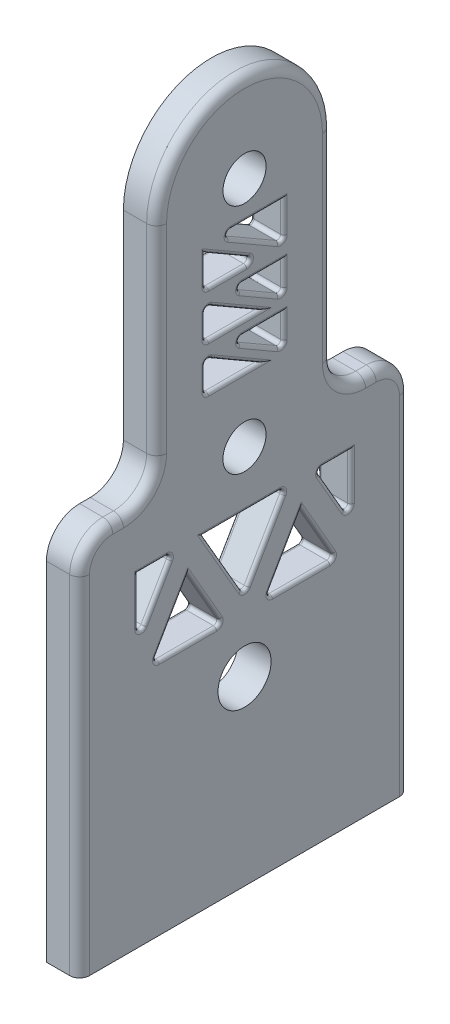
SolidWorks part; units mm, degrees
note: The reader was unsure of these and kept them because the rebuilt part matched: shared geometry of "Sketch2<15>".
ref_plane "Front Plane" through (0, 0, 0) normal (0, 0, 1) x (1, 0, 0)
ref_plane "Top Plane" through (0, 0, 0) normal (0, 1, 0) x (1, 0, 0)
ref_plane "Right Plane" through (0, 0, 0) normal (1, 0, 0) x (0, 0, -1)
sketch "Sketch2" plane through (0, 0, 0) normal (1, 0, 0) x (0, 0, -1)
  line L0 (-49.7, 0) -> (-49.7, -54.7)
  line L1 (-49.7, -54.7) -> (49.7, -54.7)
  line L2 (49.7, -54.7) -> (49.7, 0)
  line L3 (-49.7, -37.7) -> (49.7, -37.7)
  line L4 (-49.7, 0) -> (-49.7, 130)
  line L6 (49.7, 130) -> (49.7, 0)
  line L7 (-4.0065, 60) -> (3.9935, 60) construction
  line L8 (-0.0065, 60) -> (0, 130) construction
  line L9 (0, -54.7) -> (0, -37.7) construction
  line L10 (-49.7, 130) -> (49.7, 130) construction
  arc A137 (49.7, 130) -> (-49.7, 130) centre (0, 130) ccw
  circle A138 centre (-0.0065, 60) radius 6.5
  circle A139 centre (0, 130) radius 6.5
  circle A140 centre (0, 0) radius 8
  dimension "D1" = 130
  dimension "D4" = 17
  dimension "D2" = 54.7
  dimension "D3" = 70
extrude "Boss-Extrude1" add sketch "Sketch2" along normal blind 10 contours L6 A137 L4 L0 L3 L2 A140 A139 A138
sketch "Sketch10" plane through (0, 0, 0) normal (-1, 0, 0) x (0, 0, 1)
  line L0 (0, 130) -> (0.0065, 60) construction
  line L1 (0.0065, 60) -> (49.7, 60) construction
  line L2 (26.5, 130) -> (26.5, 60)
  line L3 (-49.7, 130) -> (-49.7, -54.7)
  line L4 (-49.7, -54.7) -> (49.7, -54.7)
  line L5 (49.7, -54.7) -> (49.7, 130)
  line L8 (49.7, 60) -> (49.7, 130)
  line L9 (26.5, 60) -> (49.7, 60)
  line L10 (-26.4871, 59.9951) -> (-49.6871, 59.9908)
  line L11 (-26.5, 129.9951) -> (-26.4871, 59.9951)
  line L14 (-49.7, 130) -> (-51.6635, 100)
  line L15 (-51.6635, 100) -> (-51.6635, 59.984)
  line L16 (-51.6635, 59.984) -> (-49.6871, 59.9908)
  line L20 (-49.7, -54.7) -> (49.7, -54.7)
  arc A1 (49.7, 130) -> (-49.7, 130) centre (0, 130) ccw
  arc A2 (49.7, 130) -> (-49.7, 130) centre (0, 130) ccw
  circle A4 centre (0.0065, 60) radius 6.5
  circle A5 centre (0, 130) radius 6.5
  arc A6 (26.5, 130) -> (-26.5, 129.9951) centre (0, 130) ccw
  dimension "D2" = 20
  dimension "D1" = 0
extrude "Cut-Extrude1" cut sketch "Sketch10" against normal blind 10
fillet "Fillet1" radius 10 2 edges at (5, 60, 26.5) (5, 59.9951, -26.4871)
fillet "Fillet2" radius 10 2 edges at (5, 60, 49.7) (5, 59.9908, -49.7)
fillet "Fillet4" radius 3 11 edges at (10, 100, 26.5) (10, 62.9289, 29.4289) (10, 60, 38.1) (10, 57.0711, 46.7711) (10, -2.35, 49.7) (10, -2.3537, -49.7) (10, 57.0631, -46.7717) (10, 59.993, -38.0945) (10, 62.9235, -29.4166) (10, 99.9951, -26.4945) (10, 156.5, -0.0024)
sketch "Sketch11" plane through (10, 0, 0) normal (1, 0, 0) x (0, 0, -1)
  line L0 (-0.0065, 60) -> (0, 43) construction
  line L2 (-32.0845, 43) -> (32.0845, 43)
  line L3 (-32.0845, 43) -> (-32.0845, 17)
  line L4 (-32.0845, 17) -> (32.0845, 17)
  line L5 (32.0845, 43) -> (32.0845, 17)
  line L8 (0, 43) -> (0, 17) construction
  line L11 (-27.4657, 17) -> (-17.0734, 35)
  line L12 (-17.0734, 35) -> (-6.6811, 17)
  line L13 (32.0845, 25) -> (21.6922, 43)
  line L14 (12.4546, 43) -> (-1.4018, 19)
  line L15 (-32.0845, 25) -> (-21.6922, 43)
  line L16 (-12.4546, 43) -> (1.4018, 19)
  line L17 (27.4657, 17) -> (17.0734, 35)
  line L18 (17.0734, 35) -> (5.5264, 15)
  point P4 (0, 30)
extrude "Cut-Extrude2" cut sketch "Sketch11" against normal blind 10 contours L17 L18 L4 | L13 L5 L2 | L2 L16 L14 | L12 L11 L4 | L3 L15 L2
fillet "Fillet5" radius 1 40 edges at (0, 34, 32.0845) (10, 34, 32.0845) (0, 43, 26.8883) (10, 43, 26.8883) (0, 26, 22.2695) (10, 26, 22.2695) (0, 26, 11.8772) (10, 26, 11.8772) (0, 32.214, 6.2273) (10, 32.214, 6.2273) (0, 43, 0) (10, 43, 0) (0, 26, -11.8772) (10, 26, -11.8772) (0, 26, -22.2695) (10, 26, -22.2695) (0, 43, -26.8883) (10, 43, -26.8883) (0, 34, -32.0845) (10, 34, -32.0845) (5, 25, 32.0845) (0, 34, 26.8883) (5, 43, 21.6922) (10, 34, 26.8883) (5, 17, 27.4657) (0, 17, 17.0734) (5, 17, 6.6811) (10, 17, 17.0734) (5, 21.428, 0) (0, 32.214, -6.2273) (5, 43, -12.4546) (10, 32.214, -6.2273) (5, 17, -6.6811) (0, 17, -17.0734) (5, 17, -27.4657) (10, 17, -17.0734) (5, 43, -21.6922) (0, 34, -26.8883) (5, 25, -32.0845) (10, 34, -26.8883)
sketch "Sketch13" plane through (10, 0, 0) normal (1, 0, 0) x (0, 0, -1)
  line L0 (0, 130) -> (0, 118.6831) construction
  line L1 (-11.8762, 118.6831) -> (11.8762, 118.6831)
  line L10 (-11.8762, 118.6831) -> (-11.8762, 71.3169)
  line L11 (-11.8762, 71.3169) -> (11.8762, 71.3169)
  line L12 (11.8762, 118.6831) -> (11.8762, 71.3169)
  line L13 (-11.8762, 118.6831) -> (11.8762, 104.9696)
  line L14 (11.8762, 104.9696) -> (-11.8762, 104.9696)
  line L15 (19.3403, 75.5427) -> (-4.4121, 75.5427) construction
  line L16 (-4.4121, 89.2562) -> (19.3403, 75.5427) construction
  line L21 (-12.8762, 116.9511) -> (4.4121, 106.9696) construction
  line L23 (-11.8762, 104.9696) -> (11.8762, 91.2562)
  line L24 (11.8762, 91.2562) -> (-11.8762, 91.2562)
  line L25 (-11.8762, 91.2562) -> (11.8762, 77.5427)
  line L26 (11.8762, 77.5427) -> (-11.8762, 77.5427)
  line L27 (-11.8762, 77.5427) -> (-0.0004, 70.6861)
  line L28 (-11.8762, 116.3737) -> (4.4121, 106.9696)
  line L29 (4.4121, 106.9696) -> (-11.8762, 106.9696)
  line L30 (-11.8762, 102.6602) -> (4.4121, 93.2562)
  line L31 (4.4121, 93.2562) -> (-11.8762, 93.2562)
  line L32 (-11.8762, 88.9468) -> (4.4121, 79.5427)
  line L33 (4.4121, 79.5427) -> (-11.8762, 79.5427)
  line L34 (-11.8762, 75.2333) -> (-5.0928, 71.3169)
  line L35 (-7.8762, 118.6831) -> (11.8762, 107.279)
  line L36 (11.8762, 102.9696) -> (-4.4121, 102.9696)
  line L37 (-4.4121, 102.9696) -> (11.8762, 93.5656)
  line L38 (11.8762, 89.2562) -> (-4.4121, 89.2562)
  line L39 (-4.4121, 89.2562) -> (11.8762, 79.8521)
  line L40 (11.8762, 75.5427) -> (-4.4121, 75.5427)
  line L41 (-4.4121, 75.5427) -> (2.9072, 71.3169)
  line L42 (4.4121, 106.9696) -> (-19.3403, 106.9696) construction
  line L43 (-19.3403, 106.9696) -> (4.4121, 93.2562) construction
  line L44 (4.4121, 93.2562) -> (-19.3403, 93.2562) construction
  line L45 (-19.3403, 93.2562) -> (4.4121, 79.5427) construction
  line L46 (4.4121, 79.5427) -> (-19.3403, 79.5427) construction
  line L47 (-19.3403, 79.5427) -> (10.8762, 62.0971) construction
  line L48 (-0.0004, 70.6861) -> (0, 71.3169) construction
  line L49 (-11.8762, 77.5427) -> (11.8762, 63.8292) construction
  line L50 (-4.4121, 75.5427) -> (12.8762, 65.5613) construction
  line L51 (19.3403, 89.2562) -> (-4.4121, 89.2562) construction
  line L52 (-4.4121, 102.9696) -> (19.3403, 89.2562) construction
  line L53 (19.3403, 102.9696) -> (-4.4121, 102.9696) construction
  line L54 (-10.8762, 120.4152) -> (19.3403, 102.9696) construction
  point P0 (0, 95)
  dimension "D1" = 30
  dimension "D2" = 30
  dimension "D3" = 30
  dimension "D4" = 30
  dimension "D5" = 2
  dimension "D6" = 2
extrude "Cut-Extrude5" cut sketch "Sketch13" against normal blind 10 contours L33 L32 L10 | L38 L39 L12 | L31 L30 L10 | L36 L37 L12 | L29 L28 L10 | L1 L35 L12
fillet "Fillet6" radius 1 48 edges at (0, 118.6831, -2) (10, 118.6831, -2) (0, 112.9811, -11.8762) (10, 112.9811, -11.8762) (10, 97.9582, 3.7321) (0, 93.2562, 3.7321) (10, 93.2562, 3.7321) (0, 89.2562, -3.7321) (10, 89.2562, -3.7321) (0, 84.5541, -11.8762) (10, 84.5541, -11.8762) (0, 84.2447, 3.7321) (10, 84.2447, 3.7321) (0, 79.5427, 3.7321) (10, 79.5427, 3.7321) (5, 118.6831, 7.8762) (0, 112.9811, -2) (5, 107.279, -11.8762) (10, 112.9811, -2) (5, 102.6602, 11.8762) (0, 97.9582, 11.8762) (5, 93.2562, 11.8762) (10, 97.9582, 11.8762) (5, 89.2562, 4.4121) (0, 84.5541, -3.7321) (5, 79.8521, -11.8762) (10, 84.5541, -3.7321) (5, 88.9468, 11.8762) (0, 84.2447, 11.8762) (5, 79.5427, 11.8762) (10, 84.2447, 11.8762) (5, 106.9696, 11.8762) (0, 97.9582, 3.7321) (0, 102.9696, -3.7321) (10, 102.9696, -3.7321) (0, 98.2676, -11.8762) (10, 98.2676, -11.8762) (0, 111.6717, 11.8762) (10, 111.6717, 11.8762) (0, 111.6717, 3.7321) (10, 111.6717, 3.7321) (5, 102.9696, 4.4121) (0, 98.2676, -3.7321) (5, 93.5656, -11.8762) (10, 98.2676, -3.7321) (0, 106.9696, 3.7321) (5, 106.9696, -4.4121) (10, 106.9696, 3.7321)
extrude "Cut-Extrude6" cut sketch "Sketch2<15>" along normal blind 10 contours A140
sketch "Sketch2<15>" plane through (0, 0, 0) normal (1, 0, 0) x (0, 0, -1) same geometry as "Sketch2"
